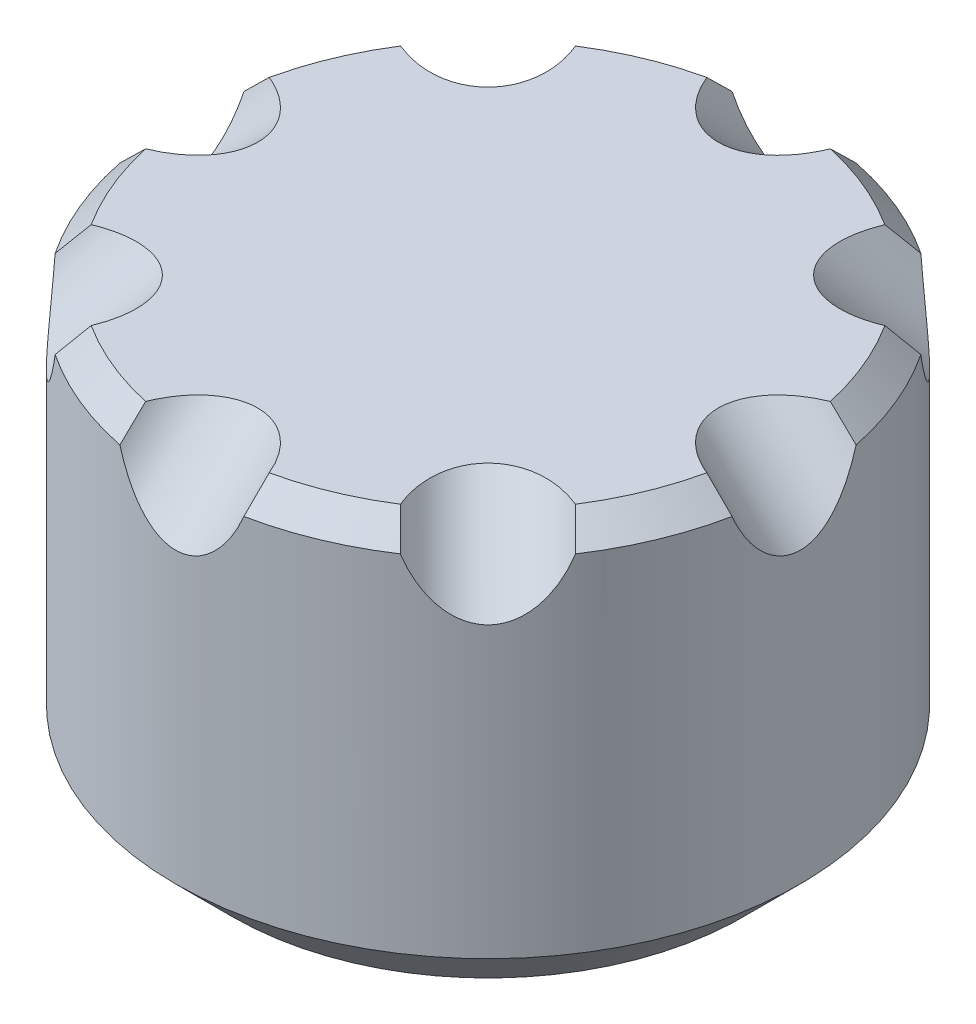
SolidWorks part; units mm, degrees
ref_plane "Front Plane" through (0, 0, 0) normal (0, 0, 1) x (1, 0, 0)
ref_plane "Top Plane" through (0, 0, 0) normal (0, 1, 0) x (1, 0, 0)
ref_plane "Right Plane" through (0, 0, 0) normal (1, 0, 0) x (0, 0, -1)
sketch "Sketch1" plane through (0, 0, 0) normal (0, 1, 0) x (1, 0, 0)
  circle A0 centre (0, 0) radius 8.75
  dimension "D1" = 17.5
extrude "Boss-Extrude1" add sketch "Sketch1" along normal blind 12
sketch "Sketch2" plane through (0, 0, 0) normal (0, -1, 0) x (1, 0, 0)
  line L0 (-2.5981, 1.5) -> (2.5981, 1.5) construction
  line L1 (-2.6439, 1.58) -> (2.6439, 1.58)
  arc A0 (-2.5981, 1.5) -> (2.5981, 1.5) centre (0, 0) ccw construction
  arc A1 (-2.6439, 1.58) -> (2.6439, 1.58) centre (0, 0) ccw
  point P5 (0, -3)
  dimension "D1" = 6
  dimension "D2" = 4.5
  dimension "D3" = 0.08
extrude "Cut-Extrude1" cut sketch "Sketch2" against normal offset from surface (11.4 mm away) 0.6 up to face at (0, 12, 8.75)
sketch "Sketch3" plane through (0, 0, 0) normal (0, -1, 0) x (1, 0, 0)
  circle A0 centre (0, 0) radius 3.08
  arc A1 (-2.6439, 1.58) -> (2.6439, 1.58) centre (0, 0) ccw construction
sketch "Sketch4" plane through (0, 0, 0) normal (0, -1, 0) x (1, 0, 0)
  circle A0 centre (0, 0) radius 4.08
  arc A1 (-2.6439, 1.58) -> (2.6439, 1.58) centre (0, 0) ccw construction
  point P7 (-2.2699, 3.28)
  dimension "D1" = 1
extrude "Cut-Extrude2" cut sketch "Sketch3" against normal offset from surface (6.9 mm away) 4.5 contours A0 up to face at (0, 11.4, -0.75)
extrude "Cut-Extrude3" cut sketch "Sketch4" against normal offset from surface (4.4 mm away) 7 up to face at (0, 11.4, -0.75)
chamfer "Chamfer1" distance 0.5 angle 30 1 edges at (0, 4.4, 3.08) first distance on face at (0, 4.4, 3.08)
chamfer "Chamfer2" distance 1.6 angle 45 1 edges at (0, 0, 8.75)
chamfer "Chamfer3" distance 0.7 angle 45 1 edges at (0, 12, 8.75)
sketch "Sketch5" plane through (0, 0, 0) normal (1, 0, 0) x (0, 0, -1)
  line L0 (7.5375, 13.7409) -> (17.4543, 3.8241) construction
  line L1 (7.5375, 13.7409) -> (7.5375, 19.1886) construction
  line L2 (5.8642, 15.4142) -> (4.45, 14)
  line L3 (4.45, 14) -> (11.5211, 6.9289)
  line L4 (11.5211, 6.9289) -> (12.9353, 8.3431)
  line L5 (5.8642, 15.4142) -> (12.9353, 8.3431)
  line L6 (8.05, 12) -> (-8.05, 12) construction
  line L8 (8.75, 1.6) -> (8.75, 11.3) construction
  dimension "D1" = 45
  dimension "D2" = 2
  dimension "D3" = 2
  dimension "D4" = 10
  dimension "D5" = 4.3
revolve "Cut-Revolve1" cut sketch "Sketch5" angle 360 about L0
pattern_circular "CirPattern1" count 8 over 360 about axis through (0, 12, 0) along (0, -1, 0) of "Cut-Revolve1" reverse direction yes
